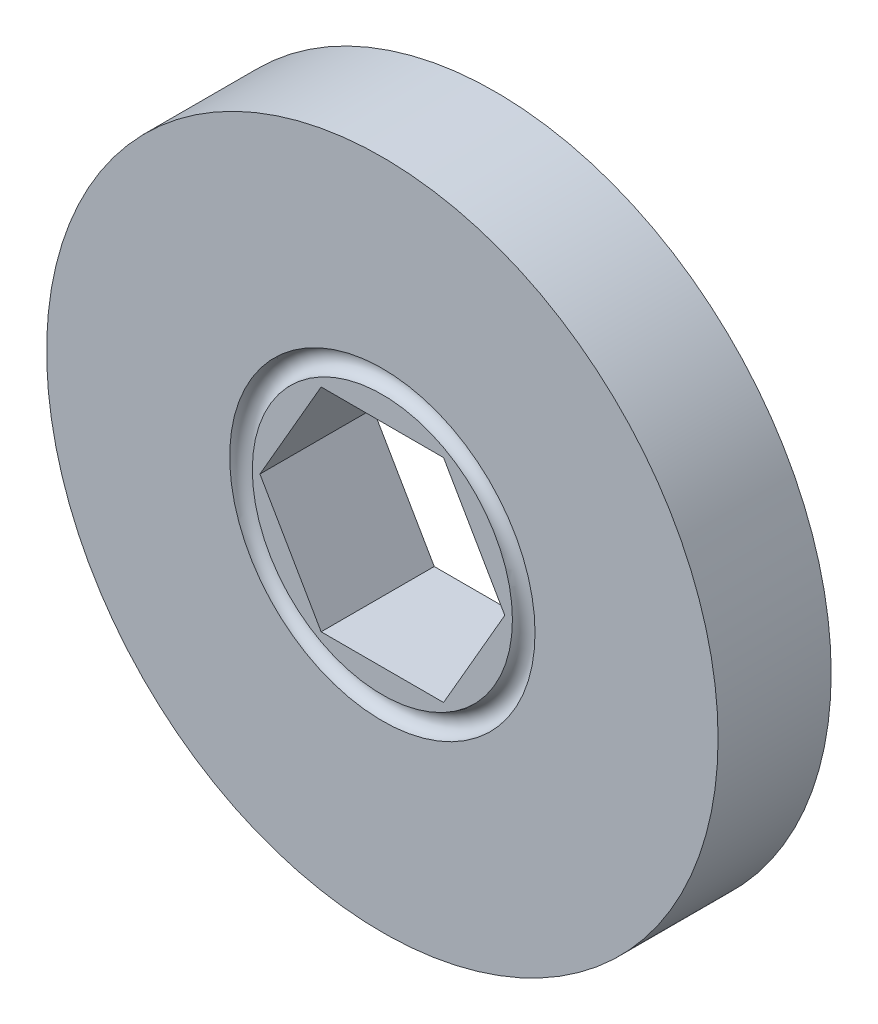
SolidWorks part; units mm, degrees
ref_plane "Front Plane" through (0, 0, 0) normal (0, 0, 1) x (1, 0, 0)
ref_plane "Top Plane" through (0, 0, 0) normal (0, 1, 0) x (1, 0, 0)
ref_plane "Right Plane" through (0, 0, 0) normal (1, 0, 0) x (0, 0, -1)
sketch "Sketch1" plane through (0, 0, 0) normal (1, 0, 0) x (0, 0, -1)
  line L0 (0, 0) -> (0, 30.1625) construction
  line L1 (-5.08, 30.1625) -> (5.08, 30.1625)
  line L2 (5.08, 30.1625) -> (5.08, 13.716)
  line L3 (5.08, 11.684) -> (5.08, 0)
  line L4 (-5.08, 11.684) -> (-5.08, 0)
  line L5 (-5.08, 30.1625) -> (-5.08, 13.716)
  line L6 (-5.08, 0) -> (5.08, 0)
  arc A0 (5.08, 13.716) -> (5.08, 11.684) centre (5.08, 12.7) ccw
  arc A1 (-5.08, 13.716) -> (-5.08, 11.684) centre (-5.08, 12.7) cw
  point P6 (0, 30.1625)
  dimension "D1" = 10.16
  dimension "D4" = 1.016
  dimension "D2" = 30.1625
  dimension "D3" = 12.7
revolve "Revolve1" add sketch "Sketch1" angle 360 about L6
sketch "Sketch2" plane through (0, 0, 5.08) normal (0, 0, 1) x (1, 0, 0)
  line L1 (-5.4993, 9.525) -> (-10.9985, 0)
  line L2 (-10.9985, 0) -> (-5.4993, -9.525)
  line L3 (-5.4993, -9.525) -> (5.4993, -9.525)
  line L4 (5.4993, -9.525) -> (10.9985, 0)
  line L5 (10.9985, 0) -> (5.4993, 9.525)
  line L6 (5.4993, 9.525) -> (-5.4993, 9.525)
  circle A0 centre (0, 0) radius 9.525 construction
  dimension "D1" = 19.05
extrude "Cut-Extrude1" cut sketch "Sketch2" against normal up to next
